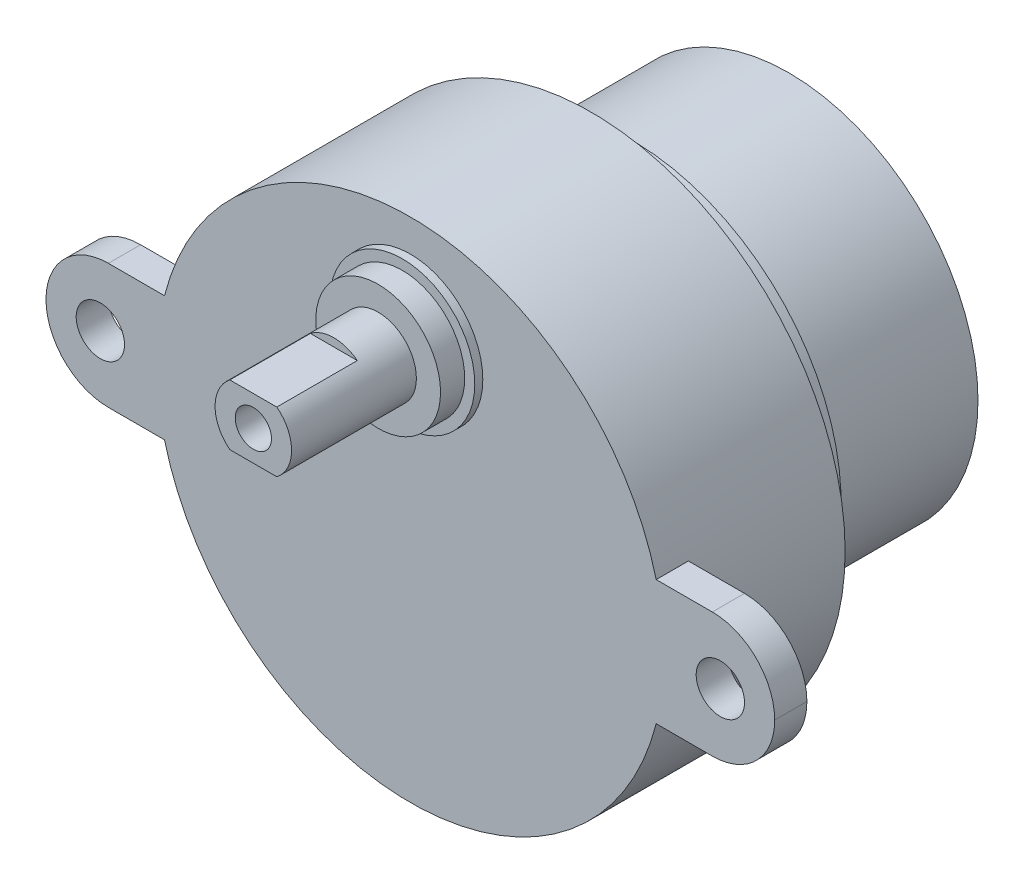
SolidWorks part; units mm, degrees
ref_plane "Front Plane" through (0, 0, 0) normal (0, 0, 1) x (1, 0, 0)
ref_plane "Top Plane" through (0, 0, 0) normal (0, 1, 0) x (1, 0, 0)
ref_plane "Right Plane" through (0, 0, 0) normal (1, 0, 0) x (0, 0, -1)
sketch "Sketch1" plane through (0, 0, 0) normal (0, 0, 1) x (1, 0, 0)
  circle A0 centre (0, 0) radius 16.002
  dimension "D1" = 32.004
extrude "Boss-Extrude1" add sketch "Sketch1" against normal blind 13.97
sketch "Sketch2" plane through (0, 0, -13.97) normal (0, 0, -1) x (-1, 0, 0)
  circle A0 centre (0, 0) radius 11.938
  dimension "D1" = 23.876
extrude "Boss-Extrude2" add sketch "Sketch2" along normal blind 9.906
sketch "Sketch3" plane through (0, 0, -13.97) normal (0, 0, -1) x (-1, 0, 0)
  circle A0 centre (0, 0) radius 13.208
  circle A1 centre (0, 0) radius 16.002
  circle A2 centre (0, 0) radius 16.002 construction
  dimension "D1" = 26.416
extrude "Cut-Extrude1" cut sketch "Sketch3" against normal blind 2.54
sketch "Sketch4" plane through (0, 0, 0) normal (0, 0, 1) x (1, 0, 0)
  line L1 (-22.987, 3.937) -> (22.987, 3.937)
  line L2 (-22.987, 3.937) -> (-22.987, -3.937)
  line L3 (-22.987, -3.937) -> (22.987, -3.937)
  line L4 (22.987, 3.937) -> (22.987, -3.937)
  line L5 (-22.987, 3.937) -> (22.987, -3.937) construction
  line L6 (-22.987, -3.937) -> (22.987, 3.937) construction
  point P0 (0, 0)
  dimension "D1" = 7.874
  dimension "D2" = 45.974
extrude "Boss-Extrude3" add sketch "Sketch4" against normal blind 2.032
sketch "Sketch5" plane through (0, 0, 0) normal (0, 0, 1) x (1, 0, 0)
  line L0 (-19.558, 0) -> (19.558, 0) construction
  circle A0 centre (-19.558, 0) radius 1.524
  circle A1 centre (19.558, 0) radius 1.524
  point P4 (0, 0)
  dimension "D2" = 3.048
  dimension "D1" = 39.116
extrude "Cut-Extrude2" cut sketch "Sketch5" against normal through all both and the other way through all
fillet "Fillet1" radius 3.937 4 edges at (22.987, 3.937, -1.016) (22.987, -3.937, -1.016) (-22.987, -3.937, -1.016) (-22.987, 3.937, -1.016)
sketch "Sketch6" plane through (0, 0, 0) normal (0, 0, 1) x (1, 0, 0)
  circle A0 centre (0, 9.398) radius 4.572
  point P2 (-1.8079, 9.2225)
  dimension "D1" = 9.398
  dimension "D2" = 9.144
extrude "Boss-Extrude4" add sketch "Sketch6" along normal blind 0.508
sketch "Sketch7" plane through (0, 0, 0) normal (0, 0, 1) x (1, 0, 0)
  circle A0 centre (0, 9.398) radius 3.937
  dimension "D1" = 7.874
extrude "Boss-Extrude5" add sketch "Sketch7" along normal blind 2.032
sketch "Sketch8" plane through (0, 0, 0) normal (0, 0, 1) x (1, 0, 0)
  circle A0 centre (0, 9.398) radius 2.413
  dimension "D1" = 4.826
extrude "Boss-Extrude6" add sketch "Sketch8" along normal blind 9.906
sketch "Sketch9" plane through (0, 0, 9.906) normal (0, 0, 1) x (1, 0, 0)
  line L0 (-1.4811, 11.303) -> (1.4811, 11.303)
  line L1 (-1.4811, 7.493) -> (1.4811, 7.493)
  circle A0 centre (0, 9.398) radius 2.413 construction
  arc A1 (-1.4811, 7.493) -> (1.4811, 7.493) centre (0, 9.398) ccw
  circle A2 centre (0, 9.398) radius 2.413 construction
  arc A3 (1.4811, 11.303) -> (-1.4811, 11.303) centre (0, 9.398) ccw
  point P11 (-2.0481, 8.1221)
  dimension "D1" = 3.81
extrude "Cut-Extrude3" cut sketch "Sketch9" against normal blind 5.08 and the other way through all
sketch "Sketch10" plane through (0, 0, 9.906) normal (0, 0, 1) x (1, 0, 0)
  circle A0 centre (0, 9.398) radius 1.143
  dimension "D1" = 2.286
extrude "Cut-Extrude4" cut sketch "Sketch10" against normal up to surface (7.874 mm away) up to face at (2.413, 9.398, 2.032)
